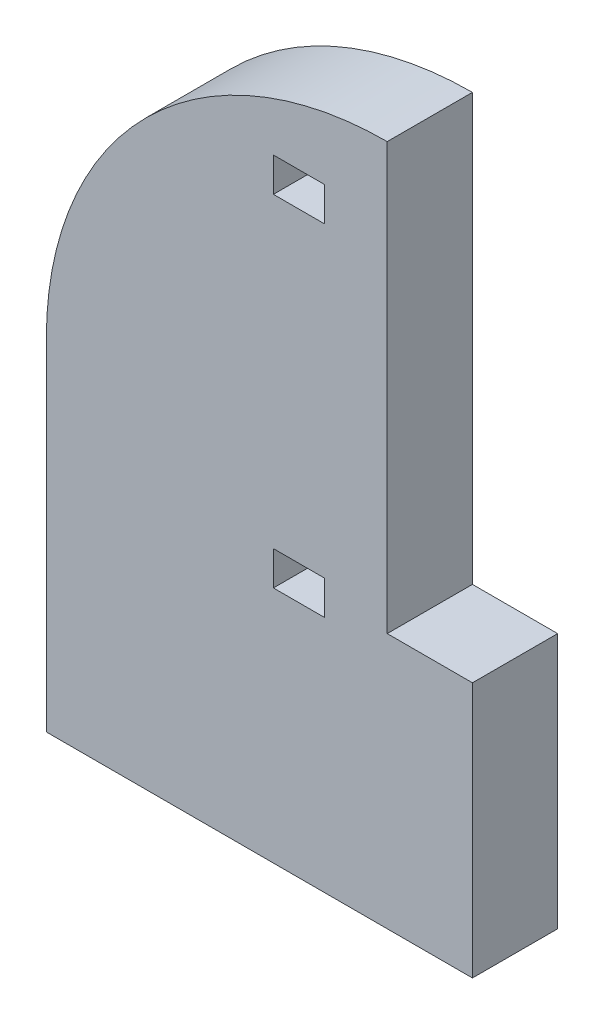
SolidWorks part; units mm, degrees
ref_plane "Front Plane" through (0, 0, 0) normal (0, 0, 1) x (1, 0, 0)
ref_plane "Top Plane" through (0, 0, 0) normal (0, 1, 0) x (1, 0, 0)
ref_plane "Right Plane" through (0, 0, 0) normal (1, 0, 0) x (0, 0, -1)
sketch "Sketch1" plane through (0, 0, 0) normal (0, 0, 1) x (1, 0, 0)
  line L0 (6.3217, -6.0204) -> (3.3217, -6.0204)
  line L1 (10, -20) -> (-10, -20)
  line L2 (10, -5) -> (10, 20)
  line L3 (10, -20) -> (15, -20)
  line L4 (-10, -20) -> (-10, 0)
  line L5 (10, -20) -> (-10, 20) construction
  line L6 (10, 20) -> (-10, -20) construction
  line L7 (6.3217, 15.9796) -> (3.3217, 15.9796)
  line L8 (10, -5) -> (15, -5)
  line L9 (15, -20) -> (15, -5)
  line L10 (6.3217, 15.9796) -> (6.3217, 13.9796)
  line L11 (6.3217, 13.9796) -> (3.3217, 13.9796)
  line L12 (3.3217, 15.9796) -> (3.3217, 13.9796)
  line L13 (3.3217, -4.0204) -> (3.3217, -6.0204)
  line L14 (6.3217, -4.0204) -> (6.3217, -6.0204)
  line L15 (6.3217, -4.0204) -> (3.3217, -4.0204)
  arc A0 (10, 20) -> (-10, 0) centre (10, 0) ccw
  point P0 (0, 0)
  dimension "D1" = 20
  dimension "D2" = 40
  dimension "D3" = 5
  dimension "D4" = 15
  dimension "D5" = 3
  dimension "D6" = 2
  dimension "D7" = 2
extrude "Boss-Extrude1" add sketch "Sketch1" along normal blind 5
